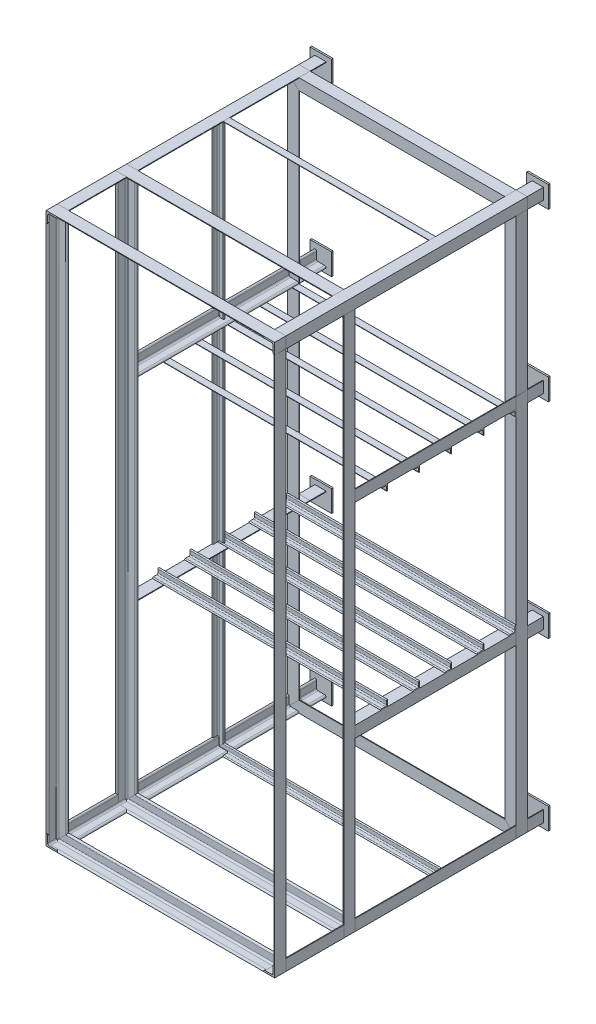
SolidWorks part; units mm, degrees
ref_plane "Front Plane" through (0, 0, 0) normal (1, 0, 0) x (0, 1, 0)
ref_plane "Top Plane" through (0, 0, 0) normal (0, 0, 1) x (0, 1, 0)
ref_plane "Right Plane" through (0, 0, 0) normal (0, 1, 0) x (-1, 0, 0)
sketch3d "3DSketch4"
  line L0 (0, 0, 0) -> (-764.7685, 0, 0) construction
  line L1 (-355, -855, 0) -> (355, -855, 0)
  line L2 (-355, -855, 0) -> (-355, 855, 0)
  line L3 (-355, 855, 0) -> (355, 855, 0)
  line L4 (355, -855, 0) -> (355, 855, 0)
  line L5 (-355, -855, 0) -> (355, 855, 0) construction
  line L6 (-355, 855, 0) -> (355, -855, 0) construction
  line L7 (355, -855, 0) -> (355, -855, 785)
  line L8 (-355, -855, 0) -> (-355, -855, 785)
  line L9 (-355, 855, 0) -> (-355, 855, 785)
  line L10 (355, 855, 0) -> (355, 855, 785)
  line L11 (355, -855, 785) -> (-355, -855, 785)
  line L12 (-355, 855, 785) -> (-355, -855, 785)
  line L13 (355, -855, 785) -> (355, 855, 785)
  line L14 (355, 855, 785) -> (-355, 855, 785)
  line L15 (355, -855, 0) -> (355, -855, -50)
  line L16 (355, 855, 0) -> (355, 855, -50)
  line L17 (-355, 855, 0) -> (-355, 855, -50)
  line L18 (-355, -855, 0) -> (-355, -855, -50)
  line L19 (-355, 855, 535) -> (-355, -855, 535)
  line L20 (-355, -855, 535) -> (355, -855, 535)
  line L21 (355, -855, 535) -> (355, 855, 535)
  line L22 (355, 855, 535) -> (-355, 855, 535)
  point P0 (0, 0, 0)
  dimension "D1" = 1710
  dimension "D2" = 710
  dimension "D4" = 50
  dimension "D3" = 785
  dimension "D5" = 250
other "Angle iron 35 X 35 X 5(3)" corner treatment miter
ref_plane "Plane3" through (355, -855, 750) normal (-1, 0, 0) x (0, 0, 1)
sketch "Sketch1" plane through (355, -855, 750) normal (-1, 0, 0) x (0, 0, 1)
  line L0 (0, 0) -> (0, 35)
  line L1 (0, 17.5) -> (5, 17.5) construction
  line L2 (5, 30) -> (5, 10)
  line L3 (10, 5) -> (30, 5)
  line L4 (17.5, 5) -> (17.5, 0) construction
  line L5 (35, 0) -> (0, 0)
  arc A0 (35, 0) -> (30, 5) centre (30, 0) ccw
  arc A1 (0, 35) -> (5, 30) centre (0, 30) cw
  arc A2 (10, 5) -> (5, 10) centre (10, 10) cw
  point P10 (17.5, 0)
  point P14 (0, 17.5)
  point P15 (5, 17.5)
  point P16 (17.5, 5)
  point P17 (5, 35)
  point P18 (35, 5)
  point P21 (0, 0)
  dimension "D2" = 5
  dimension "D3" = 35
  dimension "Radius_1" = 5
  dimension "D1" = 5
other "Angle iron 35 X 35 X 5(4)" corner treatment miter
ref_plane "Plane4" through (-355, -855, 535) normal (1, 0, 0) x (0, 1, 0)
sketch "Sketch17" plane through (-355, -855, 535) normal (1, 0, 0) x (0, 1, 0)
  line L0 (0, 0) -> (0, 35)
  line L1 (0, 17.5) -> (5, 17.5) construction
  line L2 (5, 30) -> (5, 10)
  line L3 (10, 5) -> (30, 5)
  line L4 (17.5, 5) -> (17.5, 0) construction
  line L5 (35, 0) -> (0, 0)
  arc A0 (35, 0) -> (30, 5) centre (30, 0) ccw
  arc A1 (0, 35) -> (5, 30) centre (0, 30) cw
  arc A2 (10, 5) -> (5, 10) centre (10, 10) cw
  point P10 (17.5, 0)
  point P14 (0, 17.5)
  point P15 (5, 17.5)
  point P16 (17.5, 5)
  point P17 (5, 35)
  point P18 (35, 5)
  point P21 (0, 0)
  dimension "D2" = 5
  dimension "D3" = 35
  dimension "Radius_1" = 5
  dimension "D1" = 5
other "Angle iron 35 X 35 X 5(5)" corner treatment miter
ref_plane "Plane5" through (355, -855, 35) normal (0, 1, 0) x (0, 0, -1)
sketch "Sketch18" plane through (355, -855, 35) normal (0, 1, 0) x (0, 0, -1)
  line L0 (0, 0) -> (0, 35)
  line L1 (0, 17.5) -> (5, 17.5) construction
  line L2 (5, 30) -> (5, 10)
  line L3 (10, 5) -> (30, 5)
  line L4 (17.5, 5) -> (17.5, 0) construction
  line L5 (35, 0) -> (0, 0)
  arc A0 (35, 0) -> (30, 5) centre (30, 0) ccw
  arc A1 (0, 35) -> (5, 30) centre (0, 30) cw
  arc A2 (10, 5) -> (5, 10) centre (10, 10) cw
  point P10 (17.5, 0)
  point P14 (0, 17.5)
  point P15 (5, 17.5)
  point P16 (17.5, 5)
  point P17 (5, 35)
  point P18 (35, 5)
  point P21 (0, 0)
  dimension "D2" = 5
  dimension "D3" = 35
  dimension "Radius_1" = 5
  dimension "D1" = 5
other "Angle iron 35 X 35 X 5(6)" corner treatment miter
ref_plane "Plane7" through (355, -855, 0) normal (0, 0, 1) x (0, 1, 0)
sketch "Sketch112" plane through (355, -855, 0) normal (0, 0, 1) x (0, 1, 0)
  line L0 (0, 0) -> (0, 35)
  line L1 (0, 17.5) -> (5, 17.5) construction
  line L2 (5, 30) -> (5, 10)
  line L3 (10, 5) -> (30, 5)
  line L4 (17.5, 5) -> (17.5, 0) construction
  line L5 (35, 0) -> (0, 0)
  arc A0 (35, 0) -> (30, 5) centre (30, 0) ccw
  arc A1 (0, 35) -> (5, 30) centre (0, 30) cw
  arc A2 (10, 5) -> (5, 10) centre (10, 10) cw
  point P10 (17.5, 0)
  point P14 (0, 17.5)
  point P15 (5, 17.5)
  point P16 (17.5, 5)
  point P17 (5, 35)
  point P18 (35, 5)
  point P21 (0, 0)
  dimension "D2" = 5
  dimension "D3" = 35
  dimension "Radius_1" = 5
  dimension "D1" = 5
other "Angle iron 35 X 35 X 5(8)" corner treatment miter
ref_plane "Plane8" through (-355, -855, 0) normal (0, 0, 1) x (1, 0, 0)
sketch "Sketch113" plane through (-355, -855, 0) normal (0, 0, 1) x (1, 0, 0)
  line L0 (0, 0) -> (0, 35)
  line L1 (0, 17.5) -> (5, 17.5) construction
  line L2 (5, 30) -> (5, 10)
  line L3 (10, 5) -> (30, 5)
  line L4 (17.5, 5) -> (17.5, 0) construction
  line L5 (35, 0) -> (0, 0)
  arc A0 (35, 0) -> (30, 5) centre (30, 0) ccw
  arc A1 (0, 35) -> (5, 30) centre (0, 30) cw
  arc A2 (10, 5) -> (5, 10) centre (10, 10) cw
  point P10 (17.5, 0)
  point P14 (0, 17.5)
  point P15 (5, 17.5)
  point P16 (17.5, 5)
  point P17 (5, 35)
  point P18 (35, 5)
  point P21 (0, 0)
  dimension "D2" = 5
  dimension "D3" = 35
  dimension "Radius_1" = 5
  dimension "D1" = 5
other "Angle iron 35 X 35 X 5(9)" corner treatment miter
ref_plane "Plane9" through (-355, 855, 0) normal (0, 0, -1) x (1, 0, 0)
sketch "Sketch114" plane through (-355, 855, 0) normal (0, 0, -1) x (1, 0, 0)
  line L0 (0, 0) -> (0, 35)
  line L1 (0, 17.5) -> (5, 17.5) construction
  line L2 (5, 30) -> (5, 10)
  line L3 (10, 5) -> (30, 5)
  line L4 (17.5, 5) -> (17.5, 0) construction
  line L5 (35, 0) -> (0, 0)
  arc A0 (35, 0) -> (30, 5) centre (30, 0) ccw
  arc A1 (0, 35) -> (5, 30) centre (0, 30) cw
  arc A2 (10, 5) -> (5, 10) centre (10, 10) cw
  point P10 (17.5, 0)
  point P14 (0, 17.5)
  point P15 (5, 17.5)
  point P16 (17.5, 5)
  point P17 (5, 35)
  point P18 (35, 5)
  point P21 (0, 0)
  dimension "D2" = 5
  dimension "D3" = 35
  dimension "Radius_1" = 5
  dimension "D1" = 5
other "Angle iron 35 X 35 X 5(10)" corner treatment miter
ref_plane "Plane10" through (355, 855, 0) normal (0, 0, 1) x (-1, 0, 0)
sketch "Sketch115" plane through (355, 855, 0) normal (0, 0, 1) x (-1, 0, 0)
  line L0 (0, 0) -> (0, 35)
  line L1 (0, 17.5) -> (5, 17.5) construction
  line L2 (5, 30) -> (5, 10)
  line L3 (10, 5) -> (30, 5)
  line L4 (17.5, 5) -> (17.5, 0) construction
  line L5 (35, 0) -> (0, 0)
  arc A0 (35, 0) -> (30, 5) centre (30, 0) ccw
  arc A1 (0, 35) -> (5, 30) centre (0, 30) cw
  arc A2 (10, 5) -> (5, 10) centre (10, 10) cw
  point P10 (17.5, 0)
  point P14 (0, 17.5)
  point P15 (5, 17.5)
  point P16 (17.5, 5)
  point P17 (5, 35)
  point P18 (35, 5)
  point P21 (0, 0)
  dimension "D2" = 5
  dimension "D3" = 35
  dimension "Radius_1" = 5
  dimension "D1" = 5
other "Angle iron 35 X 35 X 5(11)" corner treatment miter
ref_plane "Plane11" through (355, -855, 0) normal (0, 0, -1) x (-1, 0, 0)
sketch "Sketch116" plane through (355, -855, 0) normal (0, 0, -1) x (-1, 0, 0)
  line L0 (0, 0) -> (0, 35)
  line L1 (0, 17.5) -> (5, 17.5) construction
  line L2 (5, 30) -> (5, 10)
  line L3 (10, 5) -> (30, 5)
  line L4 (17.5, 5) -> (17.5, 0) construction
  line L5 (35, 0) -> (0, 0)
  arc A0 (35, 0) -> (30, 5) centre (30, 0) ccw
  arc A1 (0, 35) -> (5, 30) centre (0, 30) cw
  arc A2 (10, 5) -> (5, 10) centre (10, 10) cw
  point P10 (17.5, 0)
  point P14 (0, 17.5)
  point P15 (5, 17.5)
  point P16 (17.5, 5)
  point P17 (5, 35)
  point P18 (35, 5)
  point P21 (0, 0)
  dimension "D2" = 5
  dimension "D3" = 35
  dimension "Radius_1" = 5
  dimension "D1" = 5
other "Angle iron 35 X 35 X 5(12)" corner treatment miter
ref_plane "Plane12" through (-355, -855, 0) normal (0, 0, -1) x (0, 1, 0)
sketch "Sketch117" plane through (-355, -855, 0) normal (0, 0, -1) x (0, 1, 0)
  line L0 (0, 0) -> (0, 35)
  line L1 (0, 17.5) -> (5, 17.5) construction
  line L2 (5, 30) -> (5, 10)
  line L3 (10, 5) -> (30, 5)
  line L4 (17.5, 5) -> (17.5, 0) construction
  line L5 (35, 0) -> (0, 0)
  arc A0 (35, 0) -> (30, 5) centre (30, 0) ccw
  arc A1 (0, 35) -> (5, 30) centre (0, 30) cw
  arc A2 (10, 5) -> (5, 10) centre (10, 10) cw
  point P10 (17.5, 0)
  point P14 (0, 17.5)
  point P15 (5, 17.5)
  point P16 (17.5, 5)
  point P17 (5, 35)
  point P18 (35, 5)
  point P21 (0, 0)
  dimension "D2" = 5
  dimension "D3" = 35
  dimension "Radius_1" = 5
  dimension "D1" = 5
sketch3d "3DSketch6"
  line L0 (355, -300, 0) -> (355, -300, 535)
  line L1 (355, -855, 0) -> (355, 855, 0) construction
  line L2 (355, -855, 535) -> (355, 855, 535) construction
  line L3 (355, -300, 0) -> (355, -300, -50)
  line L4 (355, -855, 0) -> (355, -855, 785) construction
  line L5 (355, 300, 0) -> (355, 300, 535)
  line L6 (355, 300, 0) -> (355, 300, -50)
  dimension "D1" = 50
  dimension "D2" = 555
  dimension "D3" = 600
other "Angle iron 35 X 35 X 5(13)" corner treatment miter
ref_plane "Plane13" through (355, -300, 0) normal (0, 0, 1) x (-1, 0, 0)
sketch "Sketch118" plane through (355, -300, 0) normal (0, 0, 1) x (-1, 0, 0)
  line L0 (0, 0) -> (0, 35)
  line L1 (0, 17.5) -> (5, 17.5) construction
  line L2 (5, 30) -> (5, 10)
  line L3 (10, 5) -> (30, 5)
  line L4 (17.5, 5) -> (17.5, 0) construction
  line L5 (35, 0) -> (0, 0)
  arc A0 (35, 0) -> (30, 5) centre (30, 0) ccw
  arc A1 (0, 35) -> (5, 30) centre (0, 30) cw
  arc A2 (10, 5) -> (5, 10) centre (10, 10) cw
  point P10 (17.5, 0)
  point P14 (0, 17.5)
  point P15 (5, 17.5)
  point P16 (17.5, 5)
  point P17 (5, 35)
  point P18 (35, 5)
  point P21 (0, 0)
  dimension "D2" = 5
  dimension "D3" = 35
  dimension "Radius_1" = 5
  dimension "D1" = 5
other "Angle iron 35 X 35 X 5(14)" corner treatment miter
ref_plane "Plane14" through (355, 300, 0) normal (0, 0, 1) x (0, 1, 0)
sketch "Sketch119" plane through (355, 300, 0) normal (0, 0, 1) x (0, 1, 0)
  line L0 (0, 0) -> (0, 35)
  line L1 (0, 17.5) -> (5, 17.5) construction
  line L2 (5, 30) -> (5, 10)
  line L3 (10, 5) -> (30, 5)
  line L4 (17.5, 5) -> (17.5, 0) construction
  line L5 (35, 0) -> (0, 0)
  arc A0 (35, 0) -> (30, 5) centre (30, 0) ccw
  arc A1 (0, 35) -> (5, 30) centre (0, 30) cw
  arc A2 (10, 5) -> (5, 10) centre (10, 10) cw
  point P10 (17.5, 0)
  point P14 (0, 17.5)
  point P15 (5, 17.5)
  point P16 (17.5, 5)
  point P17 (5, 35)
  point P18 (35, 5)
  point P21 (0, 0)
  dimension "D2" = 5
  dimension "D3" = 35
  dimension "Radius_1" = 5
  dimension "D1" = 5
sketch3d "3DSketch7"
  line L0 (-355, 300, 0) -> (-355, 300, 535)
  line L1 (-355, -855, 0) -> (-355, 855, 0) construction
  line L2 (-355, 855, 535) -> (-355, -855, 535) construction
  line L3 (-355, 300, 0) -> (-355, 300, -50)
  line L4 (-355, -300, 535) -> (-355, -300, 0)
  line L5 (-355, -855, 0) -> (-355, -855, 785) construction
  line L6 (-355, -300, 0) -> (-355, -300, -50)
  dimension "D2" = 555
  dimension "D1" = 50
  dimension "D3" = 600
other "Angle iron 35 X 35 X 5(15)" corner treatment miter
ref_plane "Plane15" through (-355, 300, 0) normal (0, 0, 1) x (1, 0, 0)
sketch "Sketch120" plane through (-355, 300, 0) normal (0, 0, 1) x (1, 0, 0)
  line L0 (0, 0) -> (0, 35)
  line L1 (0, 17.5) -> (5, 17.5) construction
  line L2 (5, 30) -> (5, 10)
  line L3 (10, 5) -> (30, 5)
  line L4 (17.5, 5) -> (17.5, 0) construction
  line L5 (35, 0) -> (0, 0)
  arc A0 (35, 0) -> (30, 5) centre (30, 0) ccw
  arc A1 (0, 35) -> (5, 30) centre (0, 30) cw
  arc A2 (10, 5) -> (5, 10) centre (10, 10) cw
  point P10 (17.5, 0)
  point P14 (0, 17.5)
  point P15 (5, 17.5)
  point P16 (17.5, 5)
  point P17 (5, 35)
  point P18 (35, 5)
  point P21 (0, 0)
  dimension "D2" = 5
  dimension "D3" = 35
  dimension "Radius_1" = 5
  dimension "D1" = 5
other "Angle iron 35 X 35 X 5(16)" corner treatment miter
ref_plane "Plane16" through (-355, -300, 535) normal (0, 0, -1) x (1, 0, 0)
sketch "Sketch121" plane through (-355, -300, 535) normal (0, 0, -1) x (1, 0, 0)
  line L0 (0, 0) -> (0, 35)
  line L1 (0, 17.5) -> (5, 17.5) construction
  line L2 (5, 30) -> (5, 10)
  line L3 (10, 5) -> (30, 5)
  line L4 (17.5, 5) -> (17.5, 0) construction
  line L5 (35, 0) -> (0, 0)
  arc A0 (35, 0) -> (30, 5) centre (30, 0) ccw
  arc A1 (0, 35) -> (5, 30) centre (0, 30) cw
  arc A2 (10, 5) -> (5, 10) centre (10, 10) cw
  point P10 (17.5, 0)
  point P14 (0, 17.5)
  point P15 (5, 17.5)
  point P16 (17.5, 5)
  point P17 (5, 35)
  point P18 (35, 5)
  point P21 (0, 0)
  dimension "D2" = 5
  dimension "D3" = 35
  dimension "Radius_1" = 5
  dimension "D1" = 5
sketch3d "3DSketch8"
  line L1 (355, -855, 0) -> (355, -855, 785) construction
  line L2 (355, -855, 250) -> (-355, -855, 250)
  line L3 (-355, -855, 0) -> (-355, -855, 785) construction
  line L4 (-355, -855, 250) -> (-355, 855, 250)
  line L5 (-355, 855, 0) -> (-355, 855, 785) construction
  line L7 (-355, -855, 0) -> (-355, 855, 0) construction
  line L8 (-355, 855, 250) -> (355, 855, 250)
  line L9 (355, 855, 0) -> (355, 855, 785) construction
  line L11 (-355, 855, 0) -> (355, 855, 0) construction
  dimension "D1" = 250
other "Angle iron 20 X 20 X 3(1)" corner treatment miter
ref_plane "Plane17" through (355, -855, 250) normal (-1, 0, 0) x (0, 0, 1)
sketch "Sketch124" plane through (355, -855, 250) normal (-1, 0, 0) x (0, 0, 1)
  line L0 (0, 0) -> (0, 20)
  line L1 (0, 10) -> (3, 10) construction
  line L2 (3, 17) -> (3, 6.5)
  line L3 (6.5, 3) -> (17, 3)
  line L4 (10, 3) -> (10, 0) construction
  line L5 (20, 0) -> (0, 0)
  arc A0 (20, 0) -> (17, 3) centre (17, 0) ccw
  arc A1 (0, 20) -> (3, 17) centre (0, 17) cw
  arc A2 (6.5, 3) -> (3, 6.5) centre (6.5, 6.5) cw
  point P10 (10, 0)
  point P14 (0, 10)
  point P15 (3, 10)
  point P16 (10, 3)
  point P17 (3, 20)
  point P18 (20, 3)
  point P21 (0, 0)
  dimension "D2" = 3
  dimension "D3" = 20
  dimension "Radius_1" = 3.5
  dimension "D1" = 3
sketch3d "3DSketch9"
  line L0 (355, -300, 35) -> (-355, -300, 35)
  line L1 (355, -300, 0) -> (355, -300, 535) construction
  line L2 (355, 855, 35) -> (355, -855, 35) construction
  line L3 (-355, -300, 535) -> (-355, -300, 0) construction
  line L4 (355, -300, 135) -> (-355, -300, 135)
  line L5 (355, -300, 235) -> (-355, -300, 235)
  line L6 (355, -300, 335) -> (-355, -300, 335)
  line L7 (355, -300, 435) -> (-355, -300, 435)
  line L8 (-355, 300, 35) -> (355, 300, 35)
  line L9 (-355, 300, 0) -> (-355, 300, 535) construction
  line L10 (-355, -855, 35) -> (-355, 855, 35) construction
  line L11 (355, 300, 0) -> (355, 300, 535) construction
  line L12 (-355, 300, 135) -> (355, 300, 135)
  line L13 (-355, 300, 235) -> (355, 300, 235)
  line L14 (-355, 300, 335) -> (355, 300, 335)
  line L15 (-355, 300, 435) -> (355, 300, 435)
  dimension "D2" = 100
  dimension "D1" = 100
  dimension "D3" = 100
  dimension "D4" = 100
  dimension "D5" = 100
  dimension "D6" = 100
  dimension "D7" = 100
  dimension "D8" = 100
other "Angle iron 20 X 20 X 3(2)" corner treatment miter
ref_plane "Plane18" through (355, -300, 435) normal (-1, 0, 0) x (0, 0, 1)
sketch "Sketch125" plane through (355, -300, 435) normal (-1, 0, 0) x (0, 0, 1)
  line L0 (0, 0) -> (0, 20)
  line L1 (0, 10) -> (3, 10) construction
  line L2 (3, 17) -> (3, 6.5)
  line L3 (6.5, 3) -> (17, 3)
  line L4 (10, 3) -> (10, 0) construction
  line L5 (20, 0) -> (0, 0)
  arc A0 (20, 0) -> (17, 3) centre (17, 0) ccw
  arc A1 (0, 20) -> (3, 17) centre (0, 17) cw
  arc A2 (6.5, 3) -> (3, 6.5) centre (6.5, 6.5) cw
  point P10 (10, 0)
  point P14 (0, 10)
  point P15 (3, 10)
  point P16 (10, 3)
  point P17 (3, 20)
  point P18 (20, 3)
  point P21 (0, 0)
  dimension "D2" = 3
  dimension "D3" = 20
  dimension "Radius_1" = 3.5
  dimension "D1" = 3
other "Angle iron 20 X 20 X 3(3)" corner treatment miter
ref_plane "Plane19" through (-355, 300, 435) normal (1, 0, 0) x (0, 0, 1)
sketch "Sketch126" plane through (-355, 300, 435) normal (1, 0, 0) x (0, 0, 1)
  line L0 (0, 0) -> (0, 20)
  line L1 (0, 10) -> (3, 10) construction
  line L2 (3, 17) -> (3, 6.5)
  line L3 (6.5, 3) -> (17, 3)
  line L4 (10, 3) -> (10, 0) construction
  line L5 (20, 0) -> (0, 0)
  arc A0 (20, 0) -> (17, 3) centre (17, 0) ccw
  arc A1 (0, 20) -> (3, 17) centre (0, 17) cw
  arc A2 (6.5, 3) -> (3, 6.5) centre (6.5, 6.5) cw
  point P10 (10, 0)
  point P14 (0, 10)
  point P15 (3, 10)
  point P16 (10, 3)
  point P17 (3, 20)
  point P18 (20, 3)
  point P21 (0, 0)
  dimension "D2" = 3
  dimension "D3" = 20
  dimension "Radius_1" = 3.5
  dimension "D1" = 3
sketch "Sketch127" plane through (0, 0, -50) normal (0, 0, -1) x (1, 0, 0)
  line L0 (355, 855) -> (-355, 855) construction
  line L1 (303, 870) -> (370, 870)
  line L2 (303, 870) -> (303, 803)
  line L3 (303, 803) -> (370, 803)
  line L4 (370, 870) -> (370, 803)
  line L5 (303, 870) -> (370, 803) construction
  line L6 (303, 803) -> (370, 870) construction
  line L7 (355, 820) -> (355, 855) construction
  point P0 (336.5, 836.5)
  dimension "D1" = 67
  dimension "D2" = 67
  dimension "D3" = 15
  dimension "D4" = 15
extrude "Boss-Extrude1" add sketch "Sketch127" along normal blind 5 separate body
sketch "Sketch129" plane through (0, 0, -50) normal (0, 0, -1) x (1, 0, 0)
  line L0 (355, 335) -> (355, 300) construction
  line L1 (303, 352) -> (370, 352)
  line L2 (303, 352) -> (303, 285)
  line L3 (303, 285) -> (370, 285)
  line L4 (370, 352) -> (370, 285)
  line L5 (303, 352) -> (370, 285) construction
  line L6 (303, 285) -> (370, 352) construction
  line L7 (355, 300) -> (-355, 300) construction
  point P0 (336.5, 318.5)
  dimension "D1" = 67
  dimension "D2" = 67
  dimension "D3" = 15
  dimension "D4" = 15
extrude "Boss-Extrude2" add sketch "Sketch129" along normal blind 5 separate body
sketch "Sketch130" plane through (0, 0, -50) normal (0, 0, -1) x (1, 0, 0)
  line L0 (355, -300) -> (355, -335) construction
  line L1 (303, -285) -> (370, -285)
  line L2 (303, -285) -> (303, -352)
  line L3 (303, -352) -> (370, -352)
  line L4 (370, -285) -> (370, -352)
  line L5 (303, -285) -> (370, -352) construction
  line L6 (303, -352) -> (370, -285) construction
  line L7 (-355, -300) -> (355, -300) construction
  point P0 (336.5, -318.5)
  dimension "D1" = 67
  dimension "D2" = 67
  dimension "D3" = 15
  dimension "D4" = 15
extrude "Boss-Extrude3" add sketch "Sketch130" along normal blind 5 separate body
sketch "Sketch131" plane through (0, 0, -50) normal (0, 0, -1) x (1, 0, 0)
  line L0 (-355, -855) -> (355, -855) construction
  line L1 (303, -803) -> (370, -803)
  line L2 (303, -803) -> (303, -870)
  line L3 (303, -870) -> (370, -870)
  line L4 (370, -803) -> (370, -870)
  line L5 (303, -803) -> (370, -870) construction
  line L6 (303, -870) -> (370, -803) construction
  line L7 (355, -820) -> (355, -855) construction
  point P0 (336.5, -836.5)
  dimension "D1" = 67
  dimension "D2" = 67
  dimension "D3" = 15
  dimension "D4" = 15
extrude "Boss-Extrude4" add sketch "Sketch131" along normal blind 5 separate body
mirror "Mirror1" about plane through (0, 0, 0) normal (1, 0, 0) of "Boss-Extrude1", "Boss-Extrude2", "Boss-Extrude3", "Boss-Extrude4"
